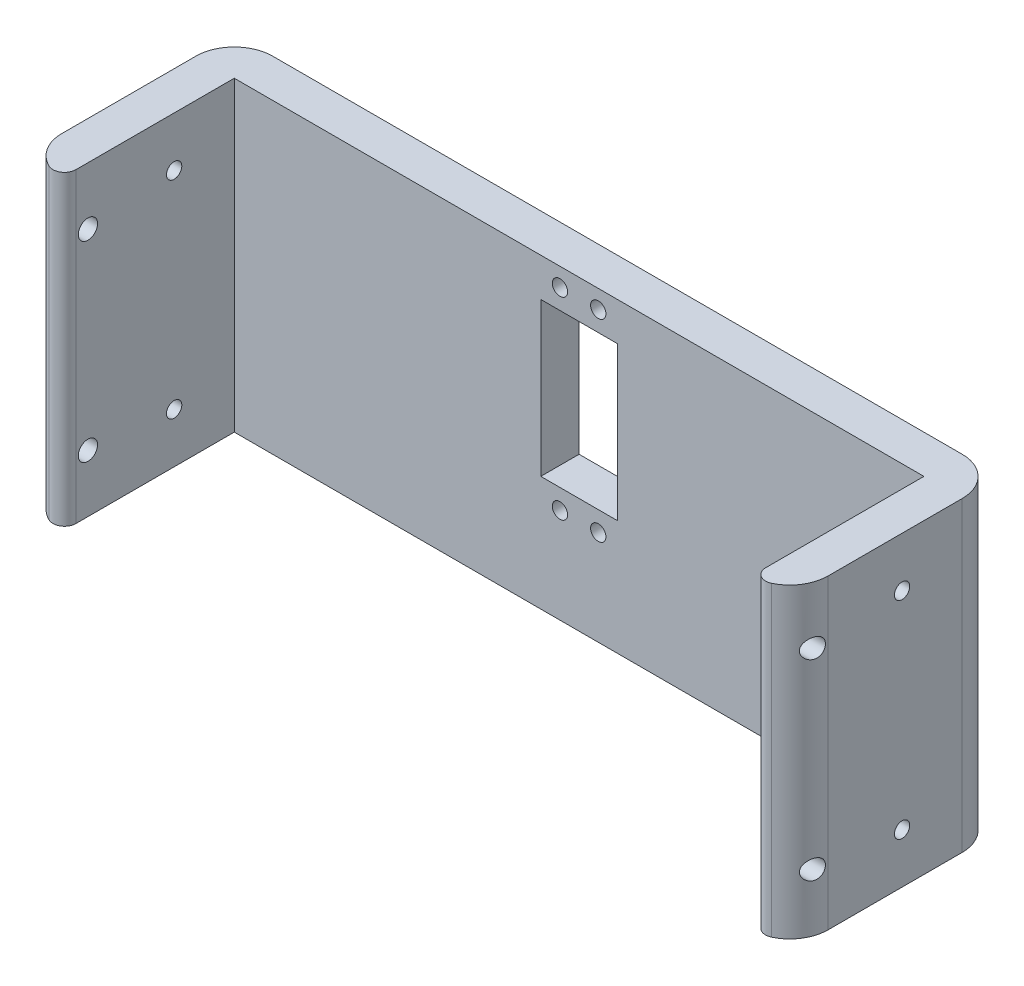
SolidWorks part; units mm, degrees
ref_plane "Plan de face" through (0, 0, 0) normal (0, 0, 1) x (1, 0, 0)
ref_plane "Plan de dessus" through (0, 0, 0) normal (0, 1, 0) x (1, 0, 0)
ref_plane "Plan de droite" through (0, 0, 0) normal (1, 0, 0) x (0, 0, -1)
sketch "Esquisse1" plane through (0, 0, 0) normal (0, 0, 1) x (1, 0, 0)
  line L1 (-100, 40) -> (100, 40)
  line L2 (-100, 40) -> (-100, -40)
  line L3 (-100, -40) -> (100, -40)
  line L4 (100, 40) -> (100, -40)
  line L5 (-100, 40) -> (100, -40) construction
  line L6 (-100, -40) -> (100, 40) construction
  point P0 (0, 0)
  dimension "D1" = 200
  dimension "D2" = 80
extrude "Boss.-Extru.1" add sketch "Esquisse1" along normal blind 10
sketch "Esquisse2" plane through (0, 0, 10) normal (0, 0, 1) x (1, 0, 0)
  line L0 (-90, 40) -> (-90, -40)
  line L1 (90, 40) -> (90, -40)
  line L2 (-90, 40) -> (-100, 40)
  line L3 (90, -40) -> (100, -40)
  line L4 (100, -40) -> (100, 40)
  line L5 (100, 40) -> (-100, 40)
  line L6 (-100, 40) -> (-100, -40)
  line L7 (-100, -40) -> (100, -40)
  line L8 (100, -40) -> (100, 40)
  line L9 (100, 40) -> (90, 40)
  line L10 (-100, 40) -> (-100, -40)
  line L11 (-100, -40) -> (-90, -40)
  dimension "D2" = 10
  dimension "D3" = 10
  dimension "D1" = 0
extrude "Boss.-Extru.2" add sketch "Esquisse2" along normal blind 50
sketch "Esquisse8" plane through (100, 0, 0) normal (1, 0, 0) x (0, 0, -1)
  line L0 (0, -40) -> (0, 40) construction
  line L1 (-60, 40) -> (0, 40) construction
  circle A0 centre (-25.7, 27) radius 2
  dimension "D3" = 4
  dimension "D1" = 25.7
  dimension "D2" = 13
extrude "Enlèv. mat.-Extru.3" cut sketch "Esquisse8" against normal through all
sketch "Esquisse9" plane through (0, 0, 60) normal (0, 0, 1) x (1, 0, 0)
  line L4 (-90, 40) -> (-100, 40)
  line L5 (-100, 40) -> (-100, -40)
  line L6 (-100, -40) -> (-90, -40)
  line L7 (-90, -40) -> (-90, 40)
  line L8 (-90, 40) -> (-100, 40)
  line L9 (-100, 40) -> (-100, -40)
  line L10 (-100, -40) -> (-90, -40)
  line L11 (-90, -40) -> (-90, 40)
  line L12 (100, -40) -> (100, 40)
  line L13 (100, 40) -> (90, 40)
  line L14 (90, 40) -> (90, -40)
  line L15 (90, -40) -> (100, -40)
  line L16 (100, -40) -> (100, 40)
  line L17 (100, 40) -> (90, 40)
  line L18 (90, 40) -> (90, -40)
  line L19 (90, -40) -> (100, -40)
  dimension "D1" = 0
  dimension "D2" = 0
extrude "Enlèv. mat.-Extru.4" cut sketch "Esquisse9" against normal blind 5
sketch "Esquisse10" plane through (90, 0, 0) normal (-1, 0, 0) x (0, 0, 1)
  line L0 (43.2, 25) -> (43.2, -25) construction
  line L1 (43.2, 25) -> (43.2, -25)
  line L2 (43.2, 25) -> (43.2, -25) construction
  line L3 (53.2, -25) -> (53.2, 25) construction
  line L4 (43.2, 25) -> (43.2, -25)
  line L5 (53.2, -25) -> (53.2, 25)
  arc A0 (43.2, -25) -> (53.2, -25) centre (48.2, -25) ccw construction
  arc A1 (53.2, 25) -> (43.2, 25) centre (48.2, 25) ccw construction
  arc A2 (43.2, -25) -> (53.2, -25) centre (48.2, -25) ccw
  arc A3 (53.2, 25) -> (43.2, 25) centre (48.2, 25) ccw
  circle A4 centre (48.2, 25) radius 2.515
  circle A5 centre (48.2, -25) radius 2.515
  dimension "D1" = 5.03
  dimension "D2" = 5.03
extrude "Enlèv. mat.-Extru.5" cut sketch "Esquisse10" against normal through all contours A4 | A5 region at (90, 25, 48.2) region at (90, -25, 48.2)
sketch "Esquisse11" plane through (-100, 0, 0) normal (-1, 0, 0) x (0, 0, 1)
  circle A0 centre (48.2, 25) radius 2.515 construction
  circle A1 centre (48.2, -25) radius 2.515 construction
  circle A2 centre (48.2, 25) radius 2.515
  circle A3 centre (48.2, -25) radius 2.515
extrude "Enlèv. mat.-Extru.6" cut sketch "Esquisse11" against normal blind 5 from offset 5 offset against normal yes
fillet "Congé1" radius 10 2 edges at (100, 0, 0) (-100, 0, 0)
fillet "Congé2" radius 10 2 edges at (100, 0, 55) (-100, 0, 55)
fillet "Congé3" radius 3 2 edges at (90, 0, 55) (-90, 0, 55)
sketch "Esquisse12" plane through (0, 0, 0) normal (0, 0, -1) x (-1, 0, 0)
  line L1 (-10, -10) -> (10, -10)
  line L2 (-10, -10) -> (-10, 30)
  line L3 (-10, 30) -> (10, 30)
  line L4 (10, -10) -> (10, 30)
extrude "Enlèv. mat.-Extru.7" cut sketch "Esquisse12" against normal through all
sketch "Esquisse13" plane through (0, 0, 10) normal (0, 0, 1) x (1, 0, 0)
  circle A0 centre (-5, 35.2) radius 2
  circle A1 centre (5, 35.2) radius 2
  circle A2 centre (-5, -15.2) radius 2
  circle A3 centre (5, -15.2) radius 2
extrude "Enlèv. mat.-Extru.8" cut sketch "Esquisse13" against normal through all
sketch "Esquisse14" plane through (-100, 0, 0) normal (-1, 0, 0) x (0, 0, 1)
  line L0 (10, 0) -> (45, 0) construction
  line L1 (10, 40) -> (10, -40) construction
  line L2 (45, -40) -> (45, 40) construction
  circle A0 centre (25.7, 27) radius 2
  circle A1 centre (25.7, -27) radius 2
extrude "Enlèv. mat.-Extru.9" cut sketch "Esquisse14" against normal through all
